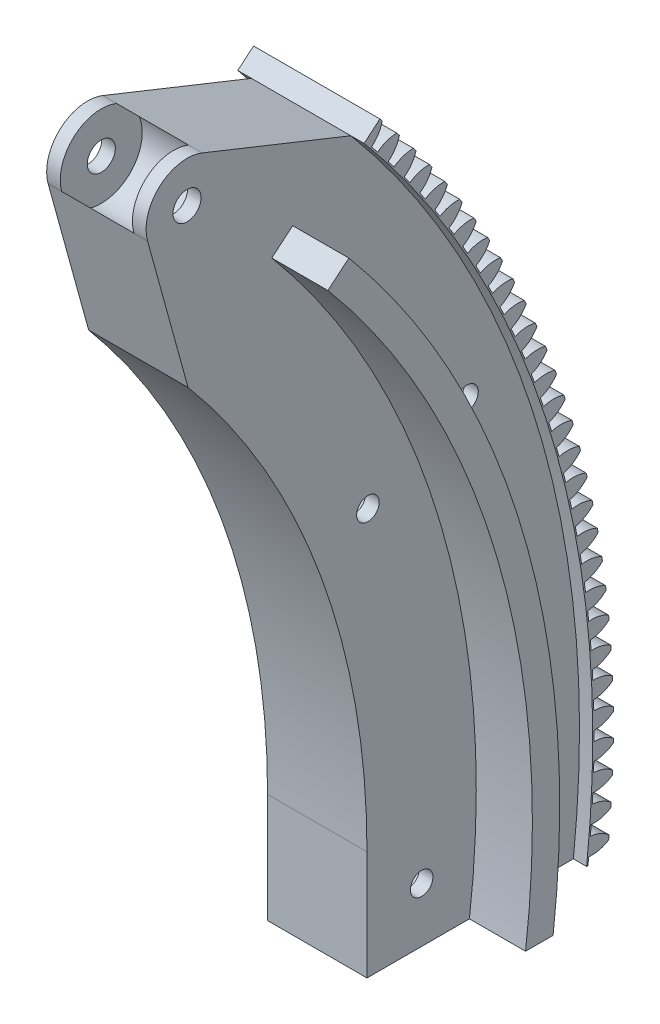
SolidWorks part; units mm, degrees
material "ABS"
ref_plane "Front Plane" through (0, 0, 0) normal (0, 0, 1) x (1, 0, 0)
ref_plane "Top Plane" through (0, 0, 0) normal (0, 1, 0) x (1, 0, 0)
ref_plane "Right Plane" through (0, 0, 0) normal (1, 0, 0) x (0, 0, -1)
ref_plane "idk" through (6.35, 0, 0) normal (1, 0, 0) x (0, 0, -1)
sketch "Sketch1" plane through (0, 0, 0) normal (1, 0, 0) x (0, 0, -1)
  line L0 (-1000, 0) -> (177.8, 0) construction
  line L1 (177.8, 0) -> (177.8, -25.4)
  line L2 (0, 0) -> (136.2027, 114.2876) construction
  line L4 (227.2, 0) -> (49000, 0) construction
  line L7 (177.8, -25.4) -> (227.2, -25.4) construction
  line L8 (227.2, 0) -> (227.2, -25.4) construction
  line L10 (-1.0719, -0.8495) -> (179.1555, 141.9904) construction
  line L61 (181.0098, 139.6187) -> (0, 0) construction
  line L62 (136.2027, 114.2876) -> (126.7844, 148.4774)
  line L64 (177.8, -25.4) -> (225.7757, -25.4)
  line L65 (136.2027, 114.2876) -> (155.124, 130.1645) construction
  line L66 (155.124, 130.1645) -> (174.0453, 146.0413) construction
  line L68 (0, 0) -> (35966.99, 34732.9185) construction
  line L69 (178.0587, 141.1212) -> (178.0836, 141.1409) construction
  line L70 (0, 0) -> (135.9673, 151.007) construction
  line L71 (139.5033, 159.8514) -> (174.0453, 146.0413)
  arc A2 (177.8, 0) -> (136.2027, 114.2876) centre (0, 0) ccw
  circle A19 centre (0, 0) radius 228.6 construction
  arc A22 (174.0453, 146.0413) -> (227.2, 0) centre (0, 0) cw
  arc A23 (227.2, 0) -> (225.7757, -25.4) centre (0, 0) cw
  arc A24 (126.7844, 148.4774) -> (139.5033, 159.8514) centre (135.9673, 151.007) cw
  point P6 (178.0836, 141.1409)
  point P7 (136.2027, 114.2876)
  dimension "D1" = 177.8
  dimension "D2" = 6.35
  dimension "D12" = 457.2
  dimension "D8" = 9.525
  dimension "D3" = 40
  dimension "D4" = 49.4
  dimension "D5" = 25.4
  dimension "D6" = 203.2
  dimension "D7" = 48
  dimension "D13" = 44
sketch "Sketch2" plane through (6.35, 0, 0) normal (1, 0, 0) x (0, 0, -1)
  line L0 (0, 0) -> (165.1, 0) construction
  line L1 (165.1, 0) -> (190.5, 0) construction
  line L2 (0, 0) -> (49240.3877, 8682.4089) construction
  circle A0 centre (165.1, 0) radius 3.2639
  circle A1 centre (190.5, 0) radius 3.2639
  arc A3 (165.1, 0) -> (162.5918, 28.6693) centre (0, 0) ccw construction
  circle A4 centre (162.5918, 28.6693) radius 3.2639
  arc A5 (190.5, 0) -> (187.6059, 33.08) centre (0, 0) ccw construction
  circle A6 centre (187.6059, 33.08) radius 3.2639
  dimension "D3" = 6.5278
  dimension "D4" = 6.5278
  dimension "D6" = 6.5278
  dimension "D7" = 6.5278
  dimension "D1" = 165.1
  dimension "D2" = 25.4
  dimension "D5" = 10
sketch "Sketch11" plane through (6.35, 0, 0) normal (1, 0, 0) x (0, 0, -1)
  line L0 (-785.502, -659.1144) -> (0, 0) construction
  line L2 (-1000, 0) -> (0, 0) construction
  line L4 (155.6602, 130.6144) -> (177.7223, 149.1267)
  line L5 (177.7223, 149.1267) -> (921.7047, 773.4021) construction
  line L6 (232, 0) -> (232, -25.4) construction
  line L7 (232, -25.4) -> (222.9391, -25.4) construction
  line L8 (201.6062, -25.4) -> (230.6054, -25.4)
  line L9 (203.2, 0) -> (232, 0) construction
  arc A0 (-230, 0) -> (-176.1902, -147.8412) centre (0, 0) ccw construction
  arc A1 (-232, 0) -> (-177.7223, -149.1267) centre (0, 0) ccw construction
  arc A2 (-229.6, 0) -> (-175.8838, -147.584) centre (0, 0) ccw construction
  arc A3 (232, 0) -> (177.7223, 149.1267) centre (0, 0) ccw
  arc A4 (230, 0) -> (176.1902, 147.8412) centre (0, 0) ccw construction
  arc A5 (-229.6, 0) -> (-175.8838, -147.584) centre (0, 0) ccw
  arc A6 (155.6602, 130.6144) -> (203.2, 0) centre (0, 0) cw
  arc A7 (232, 0) -> (230.6054, -25.4) centre (0, 0) cw
  arc A8 (203.2, 0) -> (201.6062, -25.4) centre (0, 0) cw
  dimension "D1" = 460
  dimension "D2" = 464
  dimension "D4" = 203.2
  dimension "D3" = 2.4
  dimension "D6" = 25.4
extrude "Teeth blank" add sketch "Sketch11" against normal blind 6.35 contours A3 L4 region at (6.35, 60.7212, -203.0048)
sketch "Sketch12" plane through (6.35, 0, 0) normal (1, 0, 0) x (0, 0, -1)
  line L0 (0, 0) -> (232, 0) construction
  line L2 (229.9946, 1.5708) -> (229.9946, -1.5708) construction
  line L3 (0, 0) -> (227.4972, 1.1241) construction
  line L4 (225.6789, 0) -> (232.9848, 2.6591) construction
  line L5 (0, 0) -> (232.9783, 3.1825) construction
  line L6 (229.9946, 1.5708) -> (229.9517, 4.7121) construction
  circle A0 centre (0, 0) radius 230 construction
  arc A1 (230.6054, -25.4) -> (177.7223, 149.1267) centre (0, 0) ccw construction
  circle A2 centre (0, 0) radius 227.5 construction
  arc A3 (227.4972, 1.1241) -> (232.9725, 3.5819) centre (227.4606, 8.5329) ccw
  arc A4 (231.5994, -25.5095) -> (232.9725, -3.5819) centre (0, 0) cw construction
  arc A5 (227.4972, -1.1241) -> (232.9725, -3.5819) centre (227.4606, -8.5329) cw
  arc A6 (231.5994, -25.5095) -> (178.4884, 149.7695) centre (0, 0) ccw
  arc A7 (231.5994, -25.5095) -> (232.9725, 3.5819) centre (0, 0) ccw construction
  arc A8 (227.4972, 1.1241) -> (227.4972, -1.1241) centre (0, 0) cw
  arc A9 (230.6054, -25.4) -> (177.7223, 149.1267) centre (0, 0) ccw construction
  arc A10 (232.9725, 3.5819) -> (232.9725, -3.5819) centre (0, 0) cw
  dimension "D1" = 460
  dimension "D3" = 20
  dimension "D4" = 0.783
  dimension "D5" = 4.5
  dimension "D2" = 1
extrude "Primary blank" add sketch "Sketch1" along normal blind 29.464
extrude "Tooth cut" cut sketch "Sketch12" against normal blind 6.35
pattern_circular "Tooth pattern" count 230 every 1.565 about axis through (0, 0, 0) along (1, 0, 0) of "Tooth cut"
sketch "Sketch15" plane through (6.35, 0, 0) normal (1, 0, 0) x (0, 0, -1)
  line L0 (0, 0) -> (135.9673, 151.007) construction
  line L2 (0, 0) -> (102.4673, 0) construction
  circle A0 centre (135.9673, 151.007) radius 3.2639
  dimension "D3" = 6.5278
  dimension "D1" = 203.2
  dimension "D2" = 48
extrude "Holes for top support" cut sketch "Sketch15" against normal through all both and the other way through all
sketch "Sketch22" plane through (6.35, 0, 0) normal (1, 0, 0) x (0, 0, -1)
  line L0 (0, 0) -> (135.9673, 151.007)
  line L1 (0, 0) -> (177.8, 0)
  dimension "D1" = 177.8
sketch "Sketch23" plane through (0, 0, 0) normal (1, 0, 0) x (0, 0, -1)
  line L0 (0, 0) -> (177.8, 0) construction
  line L1 (0, 0) -> (136.2027, 114.2876) construction
  line L2 (177.8, 0) -> (196.85, 0) construction
  line L3 (136.2027, 114.2876) -> (155.6602, 130.6144) construction
  line L5 (155.6602, 130.6144) -> (160.5246, 134.6961)
  line L7 (201.6062, -25.4) -> (0, 0) construction
  line L8 (208.0049, -25.4) -> (201.6062, -25.4)
  line L9 (177.8, -25.4) -> (226.0776, -25.4) construction
  arc A0 (177.8, 0) -> (136.2027, 114.2876) centre (0, 0) ccw construction
  circle A2 centre (196.85, 0) radius 6.35 construction
  arc A3 (203.2, 0) -> (155.6602, 130.6144) centre (0, 0) ccw
  arc A4 (209.55, 0) -> (160.5246, 134.6961) centre (0, 0) ccw
  circle A5 centre (215.9, 0) radius 6.35 construction
  arc A6 (203.2, 0) -> (201.6062, -25.4) centre (0, 0) cw
  arc A7 (209.55, 0) -> (208.0049, -25.4) centre (0, 0) cw
  dimension "D4" = 6.35
  dimension "D5" = 12.7
  dimension "D6" = 12.7
  dimension "D1" = 177.8
  dimension "D2" = 40
  dimension "D3" = 19.05
extrude "Thing to slide along bearings" add sketch "Sketch23" against normal blind 9.8742
ref_plane "Mirror plane" through (14.732, 0, 0) normal (1, 0, 0) x (0, 0, -1)
mirror "Mirroring slider" about plane through (14.732, 0, 0) normal (1, 0, 0) of "Thing to slide along bearings"
sketch "Sketch27" plane through (6.35, 0, 0) normal (1, 0, 0) x (0, 0, -1)
  line L2 (177.7223, 149.1267) -> (174.0453, 146.0413)
  line L3 (177.7223, 149.1267) -> (174.0453, 146.0413)
  line L7 (225.7757, -25.4) -> (226.0776, -25.4)
  line L8 (225.7757, -25.4) -> (226.0776, -25.4)
  arc A4 (227.2191, 11.3011) -> (227.0964, 13.5458) centre (0, 0) ccw
  arc A95 (231.8253, 9.0012) -> (231.7841, 10.0069) centre (0, 0) ccw
  arc A111 (227.3816, 7.3377) -> (231.8253, 9.0012) centre (227.1427, 14.7428) ccw
  arc A112 (227.3816, 7.3377) -> (231.8253, 9.0012) centre (227.1427, 14.7428) ccw
  arc A113 (231.7841, 10.0069) -> (227.2191, 11.3011) centre (227.5872, 3.9012) ccw
  arc A114 (231.7841, 10.0069) -> (227.2191, 11.3011) centre (227.5872, 3.9012) ccw
  arc A139 (227.2191, 11.3011) -> (227.0964, 13.5458) centre (0, 0) ccw
  arc A141 (227.0964, 13.5458) -> (231.493, 15.3301) centre (226.6552, 20.9417) ccw
  arc A143 (227.0964, 13.5458) -> (231.493, 15.3301) centre (226.6552, 20.9417) ccw
  arc A145 (231.493, 15.3301) -> (231.4243, 16.3343) centre (0, 0) ccw
  arc A147 (231.493, 15.3301) -> (231.4243, 16.3343) centre (0, 0) ccw
  arc A149 (231.4243, 16.3343) -> (226.8257, 17.5033) centre (227.3957, 10.1163) ccw
  arc A151 (231.4243, 16.3343) -> (226.8257, 17.5033) centre (227.3957, 10.1163) ccw
  arc A153 (226.8257, 17.5033) -> (226.6416, 19.7439) centre (0, 0) ccw
  arc A155 (226.8257, 17.5033) -> (226.6416, 19.7439) centre (0, 0) ccw
  arc A157 (226.6416, 19.7439) -> (230.9878, 21.6476) centre (225.9986, 27.1249) ccw
  arc A159 (226.6416, 19.7439) -> (230.9878, 21.6476) centre (225.9986, 27.1249) ccw
  arc A161 (230.9878, 21.6476) -> (230.8918, 22.6495) centre (0, 0) ccw
  arc A163 (230.9878, 21.6476) -> (230.8918, 22.6495) centre (0, 0) ccw
  arc A165 (230.8918, 22.6495) -> (226.2629, 23.6925) centre (227.0345, 16.3238) ccw
  arc A167 (230.8918, 22.6495) -> (226.2629, 23.6925) centre (227.0345, 16.3238) ccw
  arc A169 (226.2629, 23.6925) -> (226.0178, 25.9272) centre (0, 0) ccw
  arc A171 (226.2629, 23.6925) -> (226.0178, 25.9272) centre (0, 0) ccw
  arc A173 (226.0178, 25.9272) -> (230.3104, 27.9489) centre (225.1734, 33.2879) ccw
  arc A175 (226.0178, 25.9272) -> (230.3104, 27.9489) centre (225.1734, 33.2879) ccw
  arc A177 (230.3104, 27.9489) -> (230.1869, 28.9478) centre (0, 0) ccw
  arc A179 (230.3104, 27.9489) -> (230.1869, 28.9478) centre (0, 0) ccw
  arc A181 (230.1869, 28.9478) -> (225.5314, 29.8639) centre (226.5039, 22.5191) ccw
  arc A182 (230.1869, 28.9478) -> (225.5314, 29.8639) centre (226.5039, 22.5191) ccw
  arc A184 (225.5314, 29.8639) -> (225.2252, 32.0911) centre (0, 0) ccw
  arc A186 (225.5314, 29.8639) -> (225.2252, 32.0911) centre (0, 0) ccw
  arc A189 (231.8253, 9.0012) -> (231.7841, 10.0069) centre (0, 0) ccw
  arc A282 (225.2252, 32.0911) -> (229.461, 34.2294) centre (224.1801, 39.426) ccw
  arc A284 (225.2252, 32.0911) -> (229.461, 34.2294) centre (224.1801, 39.426) ccw
  arc A286 (229.461, 34.2294) -> (229.3104, 35.2245) centre (0, 0) ccw
  arc A288 (229.461, 34.2294) -> (229.3104, 35.2245) centre (0, 0) ccw
  arc A290 (229.3104, 35.2245) -> (224.6315, 36.0131) centre (225.8043, 28.6976) ccw
  arc A292 (229.3104, 35.2245) -> (224.6315, 36.0131) centre (225.8043, 28.6976) ccw
  arc A294 (224.6315, 36.0131) -> (224.2647, 38.2311) centre (0, 0) ccw
  arc A296 (224.6315, 36.0131) -> (224.2647, 38.2311) centre (0, 0) ccw
  arc A298 (224.2647, 38.2311) -> (228.4404, 40.4843) centre (223.0196, 45.5347) ccw
  arc A300 (224.2647, 38.2311) -> (228.4404, 40.4843) centre (223.0196, 45.5347) ccw
  arc A302 (228.4404, 40.4843) -> (228.2626, 41.4749) centre (0, 0) ccw
  arc A304 (228.4404, 40.4843) -> (228.2626, 41.4749) centre (0, 0) ccw
  arc A306 (228.2626, 41.4749) -> (223.564, 42.1355) centre (224.9362, 34.8547) ccw
  arc A308 (228.2626, 41.4749) -> (223.564, 42.1355) centre (224.9362, 34.8547) ccw
  arc A310 (223.564, 42.1355) -> (223.1367, 44.3426) centre (0, 0) ccw
  arc A312 (223.564, 42.1355) -> (223.1367, 44.3426) centre (0, 0) ccw
  arc A314 (223.1367, 44.3426) -> (227.2494, 46.709) centre (221.6926, 51.6095) ccw
  arc A316 (223.1367, 44.3426) -> (227.2494, 46.709) centre (221.6926, 51.6095) ccw
  arc A318 (227.2494, 46.709) -> (227.0446, 47.6944) centre (0, 0) ccw
  arc A320 (227.2494, 46.709) -> (227.0446, 47.6944) centre (0, 0) ccw
  arc A322 (227.0446, 47.6944) -> (222.3296, 48.2264) centre (223.9002, 40.9858) ccw
  arc A324 (227.0446, 47.6944) -> (222.3296, 48.2264) centre (223.9002, 40.9858) ccw
  arc A326 (222.3296, 48.2264) -> (221.8422, 50.421) centre (0, 0) ccw
  arc A328 (222.3296, 48.2264) -> (221.8422, 50.421) centre (0, 0) ccw
  arc A330 (221.8422, 50.421) -> (225.8887, 52.8988) centre (220.2002, 57.6457) ccw
  arc A332 (221.8422, 50.421) -> (225.8887, 52.8988) centre (220.2002, 57.6457) ccw
  arc A334 (225.8887, 52.8988) -> (225.6571, 53.8783) centre (0, 0) ccw
  arc A336 (225.8887, 52.8988) -> (225.6571, 53.8783) centre (0, 0) ccw
  arc A338 (225.6571, 53.8783) -> (220.9294, 54.2813) centre (222.6972, 47.0863) ccw
  arc A340 (225.6571, 53.8783) -> (220.9294, 54.2813) centre (222.6972, 47.0863) ccw
  arc A342 (220.9294, 54.2813) -> (220.3822, 56.4618) centre (0, 0) ccw
  arc A344 (220.9294, 54.2813) -> (220.3822, 56.4618) centre (0, 0) ccw
  arc A346 (220.3822, 56.4618) -> (224.3595, 59.0492) centre (218.5434, 63.6389) ccw
  arc A348 (220.3822, 56.4618) -> (224.3595, 59.0492) centre (218.5434, 63.6389) ccw
  arc A350 (224.3595, 59.0492) -> (224.1012, 60.022) centre (0, 0) ccw
  arc A352 (224.3595, 59.0492) -> (224.1012, 60.022) centre (0, 0) ccw
  arc A354 (224.1012, 60.022) -> (219.3643, 60.2956) centre (221.3279, 53.1516) ccw
  arc A356 (224.1012, 60.022) -> (219.3643, 60.2956) centre (221.3279, 53.1516) ccw
  arc A358 (219.3643, 60.2956) -> (218.7577, 62.4604) centre (0, 0) ccw
  arc A360 (219.3643, 60.2956) -> (218.7577, 62.4604) centre (0, 0) ccw
  arc A362 (218.7577, 62.4604) -> (222.6629, 65.1555) centre (216.7236, 69.5847) ccw
  arc A364 (218.7577, 62.4604) -> (222.6629, 65.1555) centre (216.7236, 69.5847) ccw
  arc A366 (222.6629, 65.1555) -> (222.3781, 66.1209) centre (0, 0) ccw
  arc A368 (222.6629, 65.1555) -> (222.3781, 66.1209) centre (0, 0) ccw
  arc A370 (222.3781, 66.1209) -> (217.6355, 66.265) centre (219.7935, 59.1773) ccw
  arc A372 (222.3781, 66.1209) -> (217.6355, 66.265) centre (219.7935, 59.1773) ccw
  arc A374 (217.6355, 66.265) -> (216.97, 68.4124) centre (0, 0) ccw
  arc A376 (217.6355, 66.265) -> (216.97, 68.4124) centre (0, 0) ccw
  arc A378 (216.97, 68.4124) -> (220.8001, 71.2132) centre (214.742, 75.4785) ccw
  arc A380 (216.97, 68.4124) -> (220.8001, 71.2132) centre (214.742, 75.4785) ccw
  arc A382 (220.8001, 71.2132) -> (220.4891, 72.1704) centre (0, 0) ccw
  arc A384 (220.8001, 71.2132) -> (220.4891, 72.1704) centre (0, 0) ccw
  arc A386 (220.4891, 72.1704) -> (215.7443, 72.185) centre (218.0951, 65.1589) ccw
  arc A388 (220.4891, 72.1704) -> (215.7443, 72.185) centre (218.0951, 65.1589) ccw
  arc A390 (215.7443, 72.185) -> (215.0204, 74.3134) centre (0, 0) ccw
  arc A394 (215.7443, 72.185) -> (215.0204, 74.3134) centre (0, 0) ccw
  arc A398 (215.0204, 74.3134) -> (218.7726, 77.2177) centre (212.6002, 81.3159) ccw
  arc A402 (215.0204, 74.3134) -> (218.7726, 77.2177) centre (212.6002, 81.3159) ccw
  arc A406 (218.7726, 77.2177) -> (218.4355, 78.1661) centre (0, 0) ccw
  arc A410 (218.7726, 77.2177) -> (218.4355, 78.1661) centre (0, 0) ccw
  arc A414 (218.4355, 78.1661) -> (213.692, 78.0511) centre (216.2339, 71.0918) ccw
  arc A418 (218.4355, 78.1661) -> (213.692, 78.0511) centre (216.2339, 71.0918) ccw
  arc A420 (213.692, 78.0511) -> (212.9103, 80.1589) centre (0, 0) ccw
  arc A422 (213.692, 78.0511) -> (212.9103, 80.1589) centre (0, 0) ccw
  arc A423 (212.9103, 80.1589) -> (216.5817, 83.1646) centre (210.2998, 87.0927) ccw
  arc A424 (212.9103, 80.1589) -> (216.5817, 83.1646) centre (210.2998, 87.0927) ccw
  arc A425 (216.5817, 83.1646) -> (216.2189, 84.1034) centre (0, 0) ccw
  arc A426 (216.5817, 83.1646) -> (216.2189, 84.1034) centre (0, 0) ccw
  arc A427 (216.2189, 84.1034) -> (211.4804, 83.8589) centre (214.2114, 76.9716) ccw
  arc A428 (216.2189, 84.1034) -> (211.4804, 83.8589) centre (214.2114, 76.9716) ccw
  arc A429 (211.4804, 83.8589) -> (210.6414, 85.9446) centre (0, 0) ccw
  arc A430 (211.4804, 83.8589) -> (210.6414, 85.9446) centre (0, 0) ccw
  arc A431 (210.6414, 85.9446) -> (214.2293, 89.0495) centre (207.8424, 92.8045) ccw
  arc A432 (210.6414, 85.9446) -> (214.2293, 89.0495) centre (207.8424, 92.8045) ccw
  arc A434 (214.2293, 89.0495) -> (213.841, 89.978) centre (0, 0) ccw
  arc A436 (214.2293, 89.0495) -> (213.841, 89.978) centre (0, 0) ccw
  arc A438 (213.841, 89.978) -> (209.1109, 89.6041) centre (212.029, 82.794) ccw
  arc A440 (213.841, 89.978) -> (209.1109, 89.6041) centre (212.029, 82.794) ccw
  arc A442 (209.1109, 89.6041) -> (208.2152, 91.6661) centre (0, 0) ccw
  arc A444 (209.1109, 89.6041) -> (208.2152, 91.6661) centre (0, 0) ccw
  arc A446 (208.2152, 91.6661) -> (211.717, 94.8679) centre (205.2299, 98.4471) ccw
  arc A448 (208.2152, 91.6661) -> (211.717, 94.8679) centre (205.2299, 98.4471) ccw
  arc A450 (211.717, 94.8679) -> (211.3034, 95.7855) centre (0, 0) ccw
  arc A452 (211.717, 94.8679) -> (211.3034, 95.7855) centre (0, 0) ccw
  arc A454 (211.3034, 95.7855) -> (206.5853, 95.2825) centre (209.6884, 88.5547) ccw
  arc A456 (211.3034, 95.7855) -> (206.5853, 95.2825) centre (209.6884, 88.5547) ccw
  arc A458 (206.5853, 95.2825) -> (205.6337, 97.3193) centre (0, 0) ccw
  arc A460 (206.5853, 95.2825) -> (205.6337, 97.3193) centre (0, 0) ccw
  arc A462 (205.6337, 97.3193) -> (209.0467, 100.6155) centre (202.4643, 104.0162) ccw
  arc A464 (205.6337, 97.3193) -> (209.0467, 100.6155) centre (202.4643, 104.0162) ccw
  arc A466 (209.0467, 100.6155) -> (208.6082, 101.5215) centre (0, 0) ccw
  arc A467 (209.0467, 100.6155) -> (208.6082, 101.5215) centre (0, 0) ccw
  arc A468 (208.6082, 101.5215) -> (203.9056, 100.8898) centre (207.1913, 94.2492) ccw
  arc A469 (208.6082, 101.5215) -> (203.9056, 100.8898) centre (207.1913, 94.2492) ccw
  arc A470 (203.9056, 100.8898) -> (202.8987, 102.8998) centre (0, 0) ccw
  arc A471 (203.9056, 100.8898) -> (202.8987, 102.8998) centre (0, 0) ccw
  arc A472 (202.8987, 102.8998) -> (206.2204, 106.288) centre (199.5476, 109.5076) ccw
  arc A473 (202.8987, 102.8998) -> (206.2204, 106.288) centre (199.5476, 109.5076) ccw
  arc A474 (206.2204, 106.288) -> (205.7574, 107.1817) centre (0, 0) ccw
  arc A475 (206.2204, 106.288) -> (205.7574, 107.1817) centre (0, 0) ccw
  arc A476 (205.7574, 107.1817) -> (201.0737, 106.4218) centre (204.5396, 99.8735) ccw
  arc A477 (205.7574, 107.1817) -> (201.0737, 106.4218) centre (204.5396, 99.8735) ccw
  arc A478 (201.0737, 106.4218) -> (200.0123, 108.4036) centre (0, 0) ccw
  arc A479 (201.0737, 106.4218) -> (200.0123, 108.4036) centre (0, 0) ccw
  arc A480 (200.0123, 108.4036) -> (203.2402, 111.8812) centre (196.4819, 114.9174) ccw
  arc A481 (200.0123, 108.4036) -> (203.2402, 111.8812) centre (196.4819, 114.9174) ccw
  arc A482 (203.2402, 111.8812) -> (202.7529, 112.7619) centre (0, 0) ccw
  arc A483 (203.2402, 111.8812) -> (202.7529, 112.7619) centre (0, 0) ccw
  arc A484 (202.7529, 112.7619) -> (198.0918, 111.8744) centre (201.7352, 105.4232) ccw
  arc A485 (202.7529, 112.7619) -> (198.0918, 111.8744) centre (201.7352, 105.4232) ccw
  arc A486 (198.0918, 111.8744) -> (196.9766, 113.8264) centre (0, 0) ccw
  arc A487 (198.0918, 111.8744) -> (196.9766, 113.8264) centre (0, 0) ccw
  arc A488 (196.9766, 113.8264) -> (200.1084, 117.3909) centre (193.2697, 120.2413) ccw
  arc A489 (196.9766, 113.8264) -> (200.1084, 117.3909) centre (193.2697, 120.2413) ccw
  arc A490 (200.1084, 117.3909) -> (199.5972, 118.258) centre (0, 0) ccw
  arc A491 (200.1084, 117.3909) -> (199.5972, 118.258) centre (0, 0) ccw
  arc A492 (199.5972, 118.258) -> (194.9621, 117.2435) centre (198.7804, 110.8942) ccw
  arc A493 (199.5972, 118.258) -> (194.9621, 117.2435) centre (198.7804, 110.8942) ccw
  arc A494 (194.9621, 117.2435) -> (193.794, 119.1643) centre (0, 0) ccw
  arc A495 (194.9621, 117.2435) -> (193.794, 119.1643) centre (0, 0) ccw
  arc A496 (193.794, 119.1643) -> (196.8272, 122.8131) centre (189.9132, 125.4756) ccw
  arc A497 (193.794, 119.1643) -> (196.8272, 122.8131) centre (189.9132, 125.4756) ccw
  arc A498 (196.8272, 122.8131) -> (196.2926, 123.6658) centre (0, 0) ccw
  arc A499 (196.8272, 122.8131) -> (196.2926, 123.6658) centre (0, 0) ccw
  arc A500 (196.2926, 123.6658) -> (191.6869, 122.5251) centre (195.6771, 116.2824) ccw
  arc A501 (196.2926, 123.6658) -> (191.6869, 122.5251) centre (195.6771, 116.2824) ccw
  arc A502 (191.6869, 122.5251) -> (190.4667, 124.4133) centre (0, 0) ccw
  arc A503 (191.6869, 122.5251) -> (190.4667, 124.4133) centre (0, 0) ccw
  arc A504 (190.4667, 124.4133) -> (193.3992, 128.1435) centre (186.415, 130.6162) ccw
  arc A505 (190.4667, 124.4133) -> (193.3992, 128.1435) centre (186.415, 130.6162) ccw
  arc A506 (193.3992, 128.1435) -> (192.8414, 128.9814) centre (0, 0) ccw
  arc A507 (193.3992, 128.1435) -> (192.8414, 128.9814) centre (0, 0) ccw
  arc A508 (192.8414, 128.9814) -> (188.2686, 127.7153) centre (192.4279, 121.5839) ccw
  arc A509 (192.8414, 128.9814) -> (188.2686, 127.7153) centre (192.4279, 121.5839) ccw
  arc A510 (188.2686, 127.7153) -> (186.9974, 129.5694) centre (0, 0) ccw
  arc A511 (188.2686, 127.7153) -> (186.9974, 129.5694) centre (0, 0) ccw
  arc A512 (186.9974, 129.5694) -> (189.8268, 133.3784) centre (182.7777, 135.6594) ccw
  arc A513 (186.9974, 129.5694) -> (189.8268, 133.3784) centre (182.7777, 135.6594) ccw
  arc A514 (189.8268, 133.3784) -> (189.2464, 134.2007) centre (0, 0) ccw
  arc A515 (189.8268, 133.3784) -> (189.2464, 134.2007) centre (0, 0) ccw
  arc A516 (189.2464, 134.2007) -> (184.7098, 132.8101) centre (189.0351, 126.7947) ccw
  arc A517 (189.2464, 134.2007) -> (184.7098, 132.8101) centre (189.0351, 126.7947) ccw
  arc A518 (184.7098, 132.8101) -> (183.3884, 134.6289) centre (0, 0) ccw
  arc A519 (184.7098, 132.8101) -> (183.3884, 134.6289) centre (0, 0) ccw
  arc A520 (225.7757, -25.4) -> (174.0453, 146.0413) centre (0, 0) ccw
  arc A521 (225.7757, -25.4) -> (174.0453, 146.0413) centre (0, 0) ccw
  arc A522 (227.4972, -1.1241) -> (227.4972, 1.1241) centre (0, 0) ccw
  arc A523 (227.4972, -1.1241) -> (227.4972, 1.1241) centre (0, 0) ccw
  arc A524 (227.4972, 1.1241) -> (231.9847, 2.6656) centre (227.4606, 8.5329) ccw
  arc A525 (227.4972, 1.1241) -> (231.9847, 2.6656) centre (227.4606, 8.5329) ccw
  arc A526 (231.9847, 2.6656) -> (231.9709, 3.672) centre (0, 0) ccw
  arc A527 (231.9847, 2.6656) -> (231.9709, 3.672) centre (0, 0) ccw
  arc A528 (231.9709, 3.672) -> (227.4431, 5.0904) centre (227.6088, -2.3167) ccw
  arc A529 (231.9709, 3.672) -> (227.4431, 5.0904) centre (227.6088, -2.3167) ccw
  arc A530 (227.4431, 5.0904) -> (227.3816, 7.3377) centre (0, 0) ccw
  arc A531 (227.4431, 5.0904) -> (227.3816, 7.3377) centre (0, 0) ccw
  arc A532 (231.9709, -3.672) -> (231.9847, -2.6656) centre (0, 0) ccw
  arc A533 (231.9709, -3.672) -> (231.9847, -2.6656) centre (0, 0) ccw
  arc A534 (231.9847, -2.6656) -> (227.4972, -1.1241) centre (227.4606, -8.5329) ccw
  arc A535 (231.9847, -2.6656) -> (227.4972, -1.1241) centre (227.4606, -8.5329) ccw
  arc A536 (183.3884, 134.6289) -> (186.1128, 138.5137) centre (179.004, 140.6013) ccw
  arc A537 (183.3884, 134.6289) -> (186.1128, 138.5137) centre (179.004, 140.6013) ccw
  arc A538 (186.1128, 138.5137) -> (185.5101, 139.3198) centre (0, 0) ccw
  arc A539 (186.1128, 138.5137) -> (185.5101, 139.3198) centre (0, 0) ccw
  arc A540 (185.5101, 139.3198) -> (181.0132, 137.8059) centre (185.5011, 131.9108) ccw
  arc A541 (185.5101, 139.3198) -> (181.0132, 137.8059) centre (185.5011, 131.9108) ccw
  arc A542 (181.0132, 137.8059) -> (179.6426, 139.5879) centre (0, 0) ccw
  arc A543 (181.0132, 137.8059) -> (179.6426, 139.5879) centre (0, 0) ccw
  arc A544 (179.6426, 139.5879) -> (182.2598, 143.5456) centre (175.0967, 145.4383) ccw
  arc A545 (179.6426, 139.5879) -> (182.2598, 143.5456) centre (175.0967, 145.4383) ccw
  arc A546 (182.2598, 143.5456) -> (181.6354, 144.335) centre (0, 0) ccw
  arc A547 (182.2598, 143.5456) -> (181.6354, 144.335) centre (0, 0) ccw
  arc A548 (181.6354, 144.335) -> (177.1815, 142.6988) centre (181.8288, 136.9286) ccw
  arc A549 (181.6354, 144.335) -> (177.1815, 142.6988) centre (181.8288, 136.9286) ccw
  arc A550 (177.1815, 142.6988) -> (175.7628, 144.4427) centre (0, 0) ccw
  arc A551 (177.1815, 142.6988) -> (175.7628, 144.4427) centre (0, 0) ccw
  arc A552 (175.7628, 144.4427) -> (178.2709, 148.4705) centre (171.0587, 150.1668) ccw
  arc A553 (175.7628, 144.4427) -> (178.2709, 148.4705) centre (171.0587, 150.1668) ccw
  arc A554 (178.2709, 148.4705) -> (177.7223, 149.1267) centre (0, 0) ccw
  arc A555 (178.2709, 148.4705) -> (177.7223, 149.1267) centre (0, 0) ccw
  arc A556 (226.0776, -25.4) -> (226.2629, -23.6925) centre (0, 0) ccw
  arc A557 (226.0776, -25.4) -> (226.2629, -23.6925) centre (0, 0) ccw
  arc A558 (226.2629, -23.6925) -> (230.8918, -22.6495) centre (227.0345, -16.3238) ccw
  arc A559 (226.2629, -23.6925) -> (230.8918, -22.6495) centre (227.0345, -16.3238) ccw
  arc A560 (230.8918, -22.6495) -> (230.9878, -21.6476) centre (0, 0) ccw
  arc A561 (230.8918, -22.6495) -> (230.9878, -21.6476) centre (0, 0) ccw
  arc A562 (230.9878, -21.6476) -> (226.6416, -19.7439) centre (225.9986, -27.1249) ccw
  arc A563 (230.9878, -21.6476) -> (226.6416, -19.7439) centre (225.9986, -27.1249) ccw
  arc A564 (226.6416, -19.7439) -> (226.8257, -17.5033) centre (0, 0) ccw
  arc A565 (226.6416, -19.7439) -> (226.8257, -17.5033) centre (0, 0) ccw
  arc A566 (226.8257, -17.5033) -> (231.4243, -16.3343) centre (227.3957, -10.1163) ccw
  arc A567 (226.8257, -17.5033) -> (231.4243, -16.3343) centre (227.3957, -10.1163) ccw
  arc A568 (231.4243, -16.3343) -> (231.493, -15.3301) centre (0, 0) ccw
  arc A569 (231.4243, -16.3343) -> (231.493, -15.3301) centre (0, 0) ccw
  arc A570 (231.493, -15.3301) -> (227.0964, -13.5458) centre (226.6552, -20.9417) ccw
  arc A571 (231.493, -15.3301) -> (227.0964, -13.5458) centre (226.6552, -20.9417) ccw
  arc A572 (227.0964, -13.5458) -> (227.2191, -11.3011) centre (0, 0) ccw
  arc A573 (227.0964, -13.5458) -> (227.2191, -11.3011) centre (0, 0) ccw
  arc A574 (227.2191, -11.3011) -> (231.7841, -10.0069) centre (227.5872, -3.9012) ccw
  arc A575 (227.2191, -11.3011) -> (231.7841, -10.0069) centre (227.5872, -3.9012) ccw
  arc A576 (231.7841, -10.0069) -> (231.8253, -9.0012) centre (0, 0) ccw
  arc A577 (231.7841, -10.0069) -> (231.8253, -9.0012) centre (0, 0) ccw
  arc A578 (231.8253, -9.0012) -> (227.3816, -7.3377) centre (227.1427, -14.7428) ccw
  arc A579 (231.8253, -9.0012) -> (227.3816, -7.3377) centre (227.1427, -14.7428) ccw
  arc A580 (227.3816, -7.3377) -> (227.4431, -5.0904) centre (0, 0) ccw
  arc A581 (227.3816, -7.3377) -> (227.4431, -5.0904) centre (0, 0) ccw
  arc A582 (227.4431, -5.0904) -> (231.9709, -3.672) centre (227.6088, 2.3167) ccw
  arc A583 (227.4431, -5.0904) -> (231.9709, -3.672) centre (227.6088, 2.3167) ccw
  dimension "D1" = 0
extrude "Extending teeth" add sketch "Sketch27" along normal blind 23.0187
ref_plane "Plane for cut for space for top support screws" through (6.35, 0, 0) normal (-1, 0, 0) x (0, 0, 1)
sketch "Sketch28" plane through (6.35, 0, 0) normal (1, 0, 0) x (0, 0, -1)
  circle A0 centre (135.9673, 151.007) radius 9.525
  arc A1 (139.5033, 159.8514) -> (126.7844, 148.4774) centre (135.9673, 151.007) ccw construction
extrude "Cut for space for top support screws" cut sketch "Sketch28" along normal blind 16.764
sketch "Sketch29" plane through (0, -25.4, 0) normal (0, -1, 0) x (1, 0, 0)
  line L0 (14.6844, -226.0776) -> (14.732, -177.8) construction
  line L1 (29.3687, -226.0776) -> (0, -226.0776) construction
  line L2 (29.464, -177.8) -> (0, -177.8) construction
  circle A0 centre (14.7082, -201.9388) radius 3.429
  dimension "D1" = 6.858
extrude "Magnet hole" cut sketch "Sketch29" against normal blind 12.7
sketch "Sketch30" plane through (29.464, 0, 0) normal (1, 0, 0) x (0, 0, -1)
  line L6 (155.6602, 130.6144) -> (160.5246, 134.6961)
  line L7 (208.0049, -25.4) -> (225.7757, -25.4)
  line L8 (174.0453, 146.0413) -> (139.5033, 159.8514)
  line L9 (126.7844, 148.4774) -> (136.2027, 114.2876)
  line L10 (177.8, 0) -> (177.8, -25.4)
  line L11 (177.8, -25.4) -> (201.6062, -25.4)
  line L12 (155.6602, 130.6144) -> (160.5246, 134.6961)
  line L13 (208.0049, -25.4) -> (225.7757, -25.4)
  line L14 (174.0453, 146.0413) -> (139.5033, 159.8514)
  line L15 (126.7844, 148.4774) -> (136.2027, 114.2876)
  line L16 (177.8, 0) -> (177.8, -25.4)
  line L17 (177.8, -25.4) -> (201.6062, -25.4)
  arc A5 (201.6062, -25.4) -> (155.6602, 130.6144) centre (0, 0) ccw
  arc A6 (208.0049, -25.4) -> (160.5246, 134.6961) centre (0, 0) ccw
  arc A7 (225.7757, -25.4) -> (174.0453, 146.0413) centre (0, 0) ccw
  arc A8 (139.5033, 159.8514) -> (126.7844, 148.4774) centre (135.9673, 151.007) ccw
  arc A9 (177.8, 0) -> (136.2027, 114.2876) centre (0, 0) ccw
  arc A10 (201.6062, -25.4) -> (155.6602, 130.6144) centre (0, 0) ccw
  arc A11 (208.0049, -25.4) -> (160.5246, 134.6961) centre (0, 0) ccw
  arc A12 (225.7757, -25.4) -> (174.0453, 146.0413) centre (0, 0) ccw
  arc A13 (139.5033, 159.8514) -> (126.7844, 148.4774) centre (135.9673, 151.007) ccw
  arc A14 (177.8, 0) -> (136.2027, 114.2876) centre (0, 0) ccw
  dimension "D1" = 0
extrude "Cut to make space for aluminum reinforcement plate" cut sketch "Sketch30" against normal blind 3.175
mirror "Mirroring the above cut" about plane through (14.732, 0, 0) normal (1, 0, 0) of "Cut to make space for aluminum reinforcement plate"
ref_plane "Plane1" through (23.114, 0, 0) normal (1, 0, 0) x (0, 0, -1)
sketch "Sketch31" plane through (23.114, 0, 0) normal (1, 0, 0) x (0, 0, -1)
  line L0 (215.9, -12.7) -> (190.5, -12.7) construction
  line L1 (190.5, -18.3459) -> (195.3895, -15.523)
  line L2 (195.3895, -15.523) -> (195.3895, -9.877)
  line L3 (195.3895, -9.877) -> (190.5, -7.0541)
  line L4 (190.5, -7.0541) -> (185.6105, -9.877)
  line L5 (185.6105, -9.877) -> (185.6105, -15.523)
  line L6 (155.6602, 130.6144) -> (160.5246, 134.6961)
  line L7 (208.0049, -25.4) -> (225.7757, -25.4)
  line L8 (174.0453, 146.0413) -> (139.5033, 159.8514)
  line L9 (126.7844, 148.4774) -> (136.2027, 114.2876)
  line L10 (177.8, 0) -> (177.8, -25.4)
  line L11 (177.8, -25.4) -> (201.6062, -25.4)
  line L12 (155.6602, 130.6144) -> (160.5246, 134.6961) construction
  line L13 (208.0049, -25.4) -> (225.7757, -25.4) construction
  line L14 (174.0453, 146.0413) -> (139.5033, 159.8514) construction
  line L15 (126.7844, 148.4774) -> (136.2027, 114.2876) construction
  line L16 (177.8, 0) -> (177.8, -25.4) construction
  line L17 (177.8, -25.4) -> (201.6062, -25.4) construction
  line L18 (185.6105, -15.523) -> (190.5, -18.3459)
  line L19 (211.0105, -15.523) -> (215.9, -18.3459)
  line L20 (215.9, -18.3459) -> (220.7895, -15.523)
  line L21 (220.7895, -15.523) -> (220.7895, -9.877)
  line L22 (220.7895, -9.877) -> (215.9, -7.0541)
  line L23 (215.9, -7.0541) -> (211.0105, -9.877)
  line L24 (211.0105, -9.877) -> (211.0105, -15.523)
  line L25 (180.4049, 63.8817) -> (183.6433, 68.5066)
  line L26 (183.6433, 68.5066) -> (181.2572, 73.6235)
  line L27 (181.2572, 73.6235) -> (175.6328, 74.1156)
  line L28 (175.6328, 74.1156) -> (172.3945, 69.4907)
  line L29 (172.3945, 69.4907) -> (174.7805, 64.3738)
  line L30 (174.7805, 64.3738) -> (180.4049, 63.8817)
  line L31 (197.8007, 75.1083) -> (203.4252, 74.6162)
  line L32 (203.4252, 74.6162) -> (206.6635, 79.2411)
  line L33 (206.6635, 79.2411) -> (204.2775, 84.358)
  line L34 (204.2775, 84.358) -> (198.653, 84.8501)
  line L35 (198.653, 84.8501) -> (195.4147, 80.2252)
  line L36 (195.4147, 80.2252) -> (197.8007, 75.1083)
  line L37 (201.0391, 79.7332) -> (178.0189, 68.9987) construction
  line L38 (0, 0) -> (185.6105, -9.877) construction
  line L39 (0, 0) -> (172.3945, 69.4907) construction
  circle A0 centre (190.5, -12.7) radius 4.8895 construction
  circle A1 centre (215.9, -12.7) radius 4.8895 construction
  circle A2 centre (178.0189, 68.9987) radius 4.8895 construction
  circle A3 centre (201.0391, 79.7332) radius 4.8895 construction
  arc A5 (201.6062, -25.4) -> (155.6602, 130.6144) centre (0, 0) ccw
  arc A6 (208.0049, -25.4) -> (160.5246, 134.6961) centre (0, 0) ccw
  arc A7 (225.7757, -25.4) -> (174.0453, 146.0413) centre (0, 0) ccw
  arc A8 (139.5033, 159.8514) -> (126.7844, 148.4774) centre (135.9673, 151.007) ccw
  arc A9 (177.8, 0) -> (136.2027, 114.2876) centre (0, 0) ccw
  arc A10 (201.6062, -25.4) -> (155.6602, 130.6144) centre (0, 0) ccw construction
  arc A11 (208.0049, -25.4) -> (160.5246, 134.6961) centre (0, 0) ccw construction
  arc A12 (225.7757, -25.4) -> (174.0453, 146.0413) centre (0, 0) ccw construction
  arc A13 (139.5033, 159.8514) -> (126.7844, 148.4774) centre (135.9673, 151.007) ccw construction
  arc A14 (177.8, 0) -> (136.2027, 114.2876) centre (0, 0) ccw construction
  point P0 (190.5, -12.7)
  point P26 (172.5271, 85.3657)
  point P34 (-2.5353, 0)
  point P35 (178.0189, 68.9987)
  dimension "D4" = 9.779
  dimension "D5" = 9.779
  dimension "D2" = 12.7
  dimension "D3" = 12.7
  dimension "D6" = 25.4
  dimension "D8" = 25
  dimension "D1" = 0
  dimension "D7" = 2
extrude "Embedded nut cavities" cut sketch "Sketch31" against normal blind 3.302
sketch "Sketch34" plane through (23.114, 0, 0) normal (1, 0, 0) x (0, 0, -1)
  line L0 (190.5, -12.7) -> (215.9, -12.7) construction
  line L1 (0, 0) -> (190.5, -12.7) construction
  line L2 (0, 0) -> (178.0189, 68.9987) construction
  line L6 (155.6602, 130.6144) -> (160.5246, 134.6961)
  line L7 (208.0049, -25.4) -> (225.7757, -25.4)
  line L8 (174.0453, 146.0413) -> (139.5033, 159.8514)
  line L9 (126.7844, 148.4774) -> (136.2027, 114.2876)
  line L10 (177.8, 0) -> (177.8, -25.4)
  line L11 (177.8, -25.4) -> (201.6062, -25.4)
  line L12 (155.6602, 130.6144) -> (160.5246, 134.6961) construction
  line L13 (208.0049, -25.4) -> (225.7757, -25.4) construction
  line L14 (174.0453, 146.0413) -> (139.5033, 159.8514) construction
  line L15 (126.7844, 148.4774) -> (136.2027, 114.2876) construction
  line L16 (177.8, 0) -> (177.8, -25.4) construction
  line L17 (177.8, -25.4) -> (201.6062, -25.4) construction
  circle A0 centre (190.5, -12.7) radius 2.6289
  circle A1 centre (215.9, -12.7) radius 2.6289
  circle A2 centre (178.0189, 68.9987) radius 2.6289
  circle A3 centre (201.0391, 79.7332) radius 2.6289
  arc A5 (201.6062, -25.4) -> (155.6602, 130.6144) centre (0, 0) ccw
  arc A6 (208.0049, -25.4) -> (160.5246, 134.6961) centre (0, 0) ccw
  arc A7 (225.7757, -25.4) -> (174.0453, 146.0413) centre (0, 0) ccw
  arc A8 (139.5033, 159.8514) -> (126.7844, 148.4774) centre (135.9673, 151.007) ccw
  arc A9 (177.8, 0) -> (136.2027, 114.2876) centre (0, 0) ccw
  arc A10 (201.6062, -25.4) -> (155.6602, 130.6144) centre (0, 0) ccw construction
  arc A11 (208.0049, -25.4) -> (160.5246, 134.6961) centre (0, 0) ccw construction
  arc A12 (225.7757, -25.4) -> (174.0453, 146.0413) centre (0, 0) ccw construction
  arc A13 (139.5033, 159.8514) -> (126.7844, 148.4774) centre (135.9673, 151.007) ccw construction
  arc A14 (177.8, 0) -> (136.2027, 114.2876) centre (0, 0) ccw construction
  point P16 (174.8931, 92.287)
  point P18 (-1.5567, 0)
  dimension "D2" = 12.7
  dimension "D4" = 5.2578
  dimension "D6" = 5.2578
  dimension "D3" = 12.7
  dimension "D5" = 25.4
  dimension "D8" = 25
  dimension "D1" = 0
  dimension "D7" = 2
extrude "Holes for bolts for reinforcement plate mounting" cut sketch "Sketch34" against normal through all both and the other way through all
mirror "More embedded nut cavities" about plane through (14.732, 0, 0) normal (1, 0, 0) of "Embedded nut cavities"
equation "\"Module\"= 2mm"
equation "\"Number of Teeth\"= 230"
equation "\"D1@Sketch12\"=\"Module\" * \"Number of Teeth\""
equation "\"D4@Sketch12\"=180 / \"Number of Teeth\""
equation "\"D2\"= 360 / \"Number of Teeth\""
equation "\"D2@Sketch11\"=( \"Number of Teeth\" + 2) * \"Module\""
equation "\"D2@Tooth pattern\" = 360 / \"Number of Teeth\""
equation "\"D5@Sketch12\"= 2.25 * \"Module\""
equation "\"D1@Tooth pattern\" = \"Number of Teeth\""
